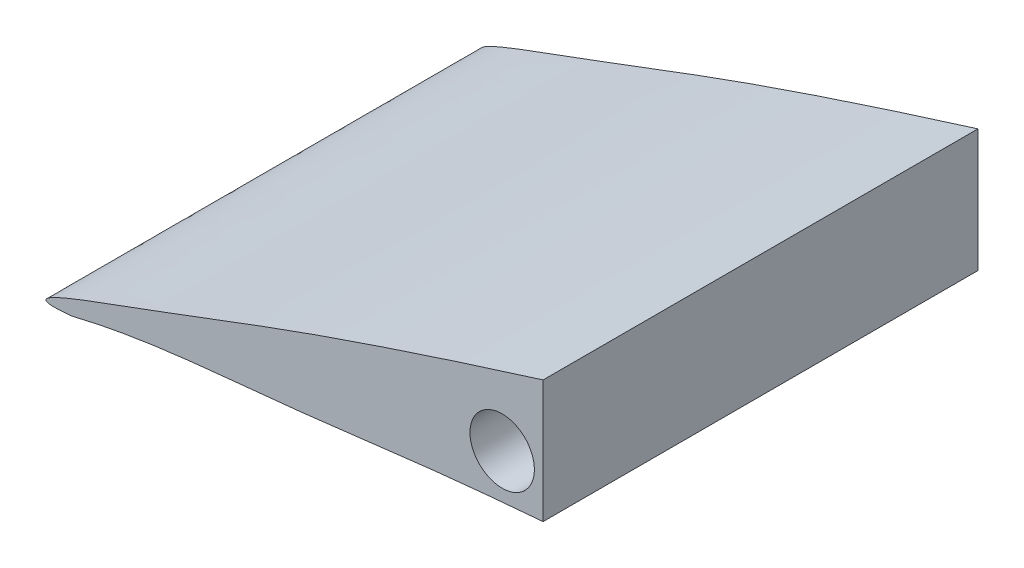
SolidWorks part; units mm, degrees
ref_plane "Front Plane" through (0, 0, 0) normal (0, 0, 1) x (1, 0, 0)
ref_plane "Top Plane" through (0, 0, 0) normal (0, 1, 0) x (1, 0, 0)
ref_plane "Right Plane" through (0, 0, 0) normal (1, 0, 0) x (0, 0, -1)
sketch "Sketch1" plane through (0, 0, 0) normal (0, 0, 1) x (1, 0, 0)
  line L0 (42.9183, -0.4477) -> (42.9183, 8.2631)
  circle A0 centre (-19.1025, -6.0109) radius 2
  circle A1 centre (12.6475, 4.4031) radius 2.127
  arc A2 (37.8951, -5.5274) -> (42.9183, -0.4477) centre (37.8383, -0.4477) ccw
  arc A3 (42.9183, 8.2631) -> (36.6811, 13.2095) centre (37.8383, 8.2631) ccw
  circle A4 centre (33.8935, 3.4217) radius 2.032
  spline S0 degree 3 poles (36.6811, 13.2095) (19.8298, 9.2672) (-2.0736, 3.8441) (-31.0965, -5.5459) (-39.3168, -8.8066) (-49.5156, -12.4957) (-45.7725, -12.1069) knots 0.118069 0.118069 0.118069 0.118069 0.630725 0.824214 0.940085 1 1 1 1
  spline S1 degree 3 poles (-45.7725, -12.1069) (-41.3374, -10.9993) (-33.8316, -10.53) (-20.4835, -8.7075) (-8.8734, -8.0192) (11.5246, -6.0282) (26.0673, -5.6598) (37.8951, -5.5274) knots 0 0 0 0 0.144322 0.237948 0.427123 0.512832 0.887818 0.887818 0.887818 0.887818
  dimension "D2" = 4
  dimension "D1" = 83.6676
extrude "Boss-Extrude1" add sketch "Sketch1" along normal blind 26.9875
sketch "Sketch2" plane through (0, 0, 26.9875) normal (0, 0, 1) x (1, 0, 0)
  line L1 (-16.5625, 14.1188) -> (88.17, 14.1188)
  line L2 (-16.5625, 14.1188) -> (-16.5625, -18.8296)
  line L3 (-16.5625, -18.8296) -> (88.17, -18.8296)
  line L4 (88.17, 14.1188) -> (88.17, -18.8296)
  dimension "D1" = 29.21
extrude "Cut-Extrude1" cut sketch "Sketch2" against normal blind 27.0764
